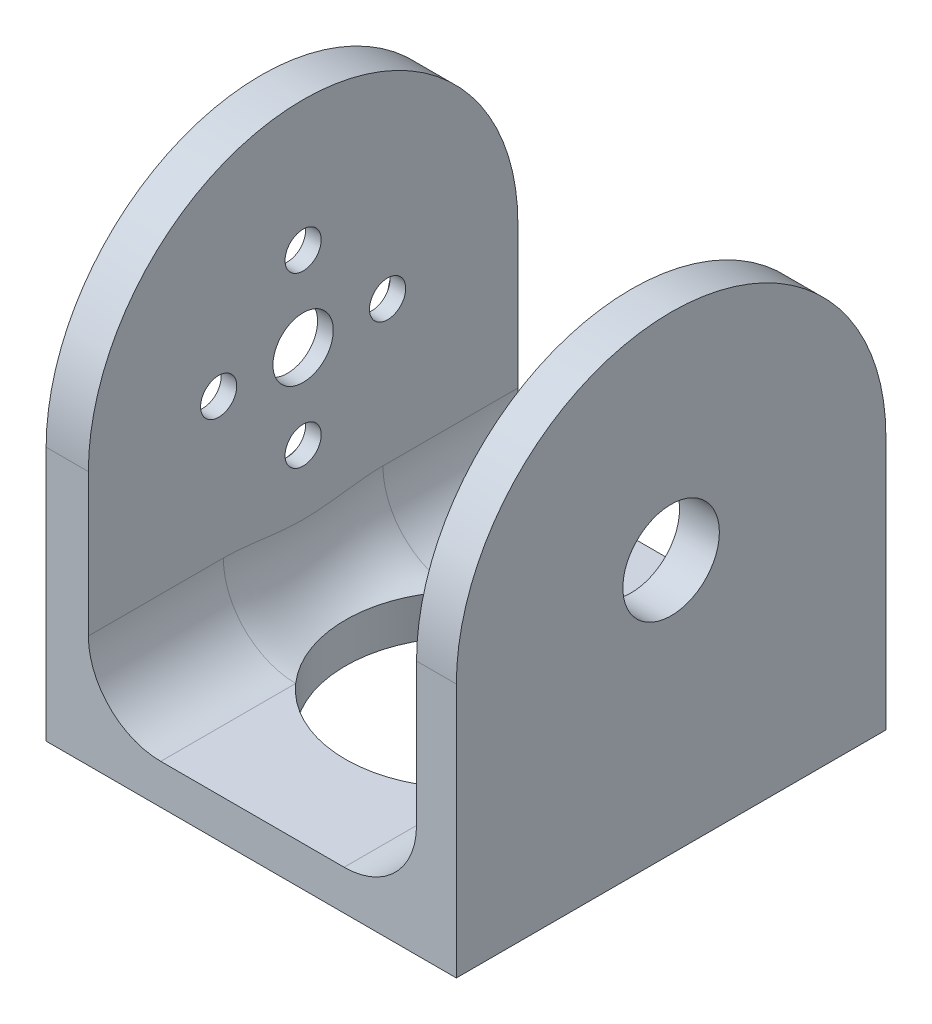
SolidWorks part; units mm, degrees
ref_plane "Front Plane" through (0, 0, 0) normal (0, 0, 1) x (1, 0, 0)
ref_plane "Top Plane" through (0, 0, 0) normal (0, 1, 0) x (1, 0, 0)
ref_plane "Right Plane" through (0, 0, 0) normal (1, 0, 0) x (0, 0, -1)
sketch "Sketch1" plane through (0, 0, 0) normal (0, 1, 0) x (1, 0, 0)
  line L1 (-17, -17.8) -> (17, -17.8)
  line L2 (-17, -17.8) -> (-17, 17.8)
  line L3 (-17, 17.8) -> (17, 17.8)
  line L4 (17, -17.8) -> (17, 17.8)
  line L5 (-17, -17.8) -> (17, 17.8) construction
  line L6 (-17, 17.8) -> (17, -17.8) construction
  point P0 (0, 0)
  dimension "D1" = 35.6
  dimension "D2" = 34
extrude "Boss-Extrude1" add sketch "Sketch1" along normal blind 3.3
sketch "Sketch3" plane through (-17, 0, 0) normal (-1, 0, 0) x (0, 0, 1)
  line L0 (0, 0) -> (0, 38.9) construction
  line L1 (-17.8, 3.3) -> (-17.8, 21.1)
  line L2 (17.8, 3.3) -> (17.8, 21.1)
  line L3 (-17.8, 3.3) -> (18.167, 3.3)
  arc A0 (-17.8, 21.1) -> (17.8, 21.1) centre (0, 21.1) cw
  line M3 (17.8, 3.3) -> (-17.8, 3.3)
  dimension "D1" = 17.8
extrude "Boss-Extrude2" add sketch "Sketch3" against normal blind 3.5 contours L0 L2 A0 M3 | L3 L0 A0 L1 region at (-17, 19.4384, -8.3081) region at (-17, 19.4384, 8.3081)
extrude "Boss-Extrude3" add sketch "Sketch3<4>" along normal blind 3.3 from surface contours L3 L0 A0 L1 | L0 L2 A0 M3 region at (-17, 19.4384, -8.3081) region at (-17, 19.4384, 8.3081) starting at face at (17, 1.65, 0)
sketch "Sketch3<4>" plane through (-17, 0, 0) normal (-1, 0, 0) x (0, 0, 1) same geometry as "Sketch3"
sketch "Sketch4" plane through (-17, 0, 0) normal (-1, 0, 0) x (0, 0, 1)
  line L0 (0, 38.9) -> (0, 0) construction
  line L1 (-17.8, 0) -> (17.8, 0) construction
  line L2 (-10.925, 21.1) -> (10.925, 21.1) construction
  circle A0 centre (0, 21.1) radius 10.925
  arc A1 (17.8, 21.1) -> (-17.8, 21.1) centre (0, 21.1) ccw construction
  circle A2 centre (0, 28.1) radius 1.5
  circle A3 centre (0, 14.1) radius 1.5
  circle A4 centre (-7, 21.1) radius 1.5
  circle A5 centre (7, 21.1) radius 1.5
  circle A6 centre (0, 21.1) radius 2.5
  dimension "D1" = 21.85
  dimension "D2" = 3
  dimension "D3" = 3
  dimension "D4" = 3
  dimension "D5" = 3
  dimension "D6" = 5
  dimension "D7" = 7
  dimension "D8" = 7
  dimension "D9" = 7
  dimension "D10" = 7
extrude "Cut-Extrude1" cut sketch "Sketch4" against normal blind 12 contours A6 | A5 | A2 | A4 | A3 region at (-17, 28.1, 0) region at (-17, 14.1, 0) region at (-17, 21.1, -7) region at (-17, 21.1, 7) region at (-17, 21.1, 0)
extrude "Cut-Extrude2" cut sketch "Sketch4<3>" against normal blind 2.2
sketch "Sketch4<3>" plane through (-17, 0, 0) normal (-1, 0, 0) x (0, 0, 1) same geometry as "Sketch4"
sketch "Sketch5" plane through (17, 0, 0) normal (1, 0, 0) x (0, 0, -1)
  line L0 (0, 38.9) -> (0, 0) construction
  arc A0 (17.8, 21.1) -> (-17.8, 21.1) centre (0, 21.1) ccw construction
  circle A1 centre (0, 21.1) radius 4
  dimension "D1" = 8
extrude "Cut-Extrude3" cut sketch "Sketch5" against normal blind 12.2
sketch "Sketch6" plane through (0, 0, 0) normal (0, -1, 0) x (1, 0, 0)
  circle A0 centre (0, 0) radius 10
  dimension "D1" = 20
extrude "Cut-Extrude4" cut sketch "Sketch6" against normal through all both and the other way through all
fillet "Fillet1" radius 6 2 edges at (13.7, 3.3, 0) (-13.5, 3.3, 0)
